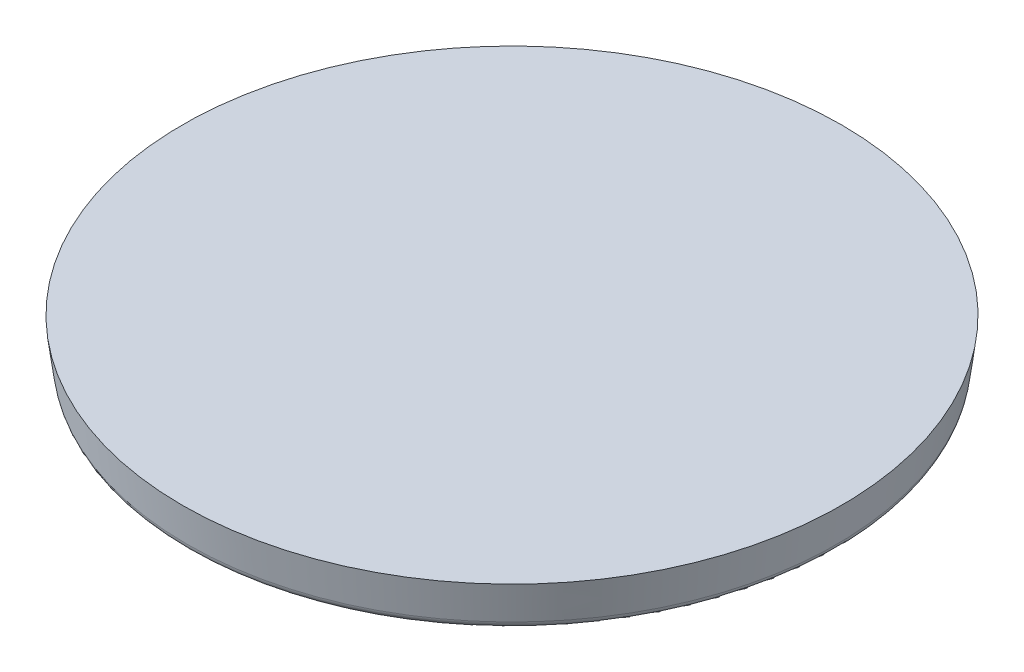
SolidWorks part; units mm, degrees
ref_plane "Front Plane" through (0, 0, 0) normal (0, 0, 1) x (1, 0, 0)
ref_plane "Top Plane" through (0, 0, 0) normal (0, 1, 0) x (1, 0, 0)
ref_plane "Right Plane" through (0, 0, 0) normal (1, 0, 0) x (0, 0, -1)
sketch "Sketch2" plane through (0, 0, 0) normal (0, 0, 1) x (1, 0, 0)
  line L0 (0, 0) -> (14.097, 0)
  line L1 (14.097, 0) -> (14.3478, 1.905)
  line L2 (14.3478, 1.905) -> (0, 1.905)
  line L4 (0, 1.905) -> (0, 0) construction
  line L5 (0, 1.905) -> (0, 0)
  dimension "D1" = 1.905
  dimension "D2" = 28.194
  dimension "D3" = 7.5
revolve "Revolve1" add sketch "Sketch2" angle 360 about L4
sketch "Sketch3" plane through (0, 0, 0) normal (0, -1, 0) x (1, 0, 0)
  line L0 (0, -0.7937) -> (0, 0.7937) construction
  line L1 (-3.0742, 0.7937) -> (3.0742, 0.7937)
  line L3 (-3.0742, -0.7937) -> (3.0742, -0.7937)
  arc A0 (-3.0742, -0.7937) -> (3.0742, -0.7937) centre (0, 0) ccw
  arc A1 (3.0742, 0.7937) -> (-3.0742, 0.7937) centre (0, 0) ccw
  point P5 (0, 0)
  point P6 (0, 0)
  point P10 (0, 0)
  point P11 (0, 0)
  dimension "D1" = 6.35
  dimension "D2" = 1.5875
extrude "Boss-Extrude1" add sketch "Sketch3" along normal blind 2.54
fillet "Fillet1" radius 2.54 2 edges at (0, 0, -3.175) (0, 0, 3.175)
fillet "Match Tool Radius" radius 0.381 1 edges at (0, 0, 14.097)
